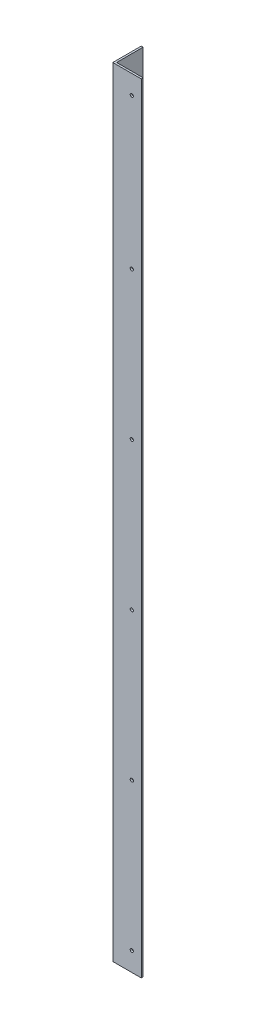
SolidWorks part; units mm, degrees
material "6063-O"
ref_plane "Piano frontale" through (0, 0, 0) normal (0, 0, 1) x (1, 0, 0)
ref_plane "Piano superiore" through (0, 0, 0) normal (0, 1, 0) x (1, 0, 0)
ref_plane "Piano destro" through (0, 0, 0) normal (1, 0, 0) x (0, 0, -1)
sketch "Schizzo2" plane through (0, 0, 0) normal (0, 1, 0) x (1, 0, 0)
  line L0 (0, 0) -> (30, 0)
  line L1 (30, 0) -> (30, 2)
  line L2 (30, 2) -> (2, 2)
  line L3 (2, 2) -> (2, 30)
  line L4 (2, 30) -> (0, 30)
  line L5 (0, 30) -> (0, 0)
  dimension "D1" = 30
  dimension "D2" = 30
  dimension "D3" = 2
  dimension "D4" = 2
extrude "Estrusione-Estrusione1" add sketch "Schizzo2" along normal blind 819
sketch "Schizzo3" plane through (0, 0, 0) normal (0, 0, 1) x (1, 0, 0)
  line L0 (20, 843.1808) -> (20, -52.7752) construction
  line L1 (0, 819) -> (0, 0) construction
  line L2 (0, 0) -> (30, 0) construction
  circle A0 centre (20, 20) radius 1.7
  circle A1 centre (20, 330.4) radius 1.7
  circle A2 centre (20, 485.6) radius 1.7
  circle A3 centre (20, 175.2) radius 1.7
  circle A4 centre (20, 640.8) radius 1.7
  circle A5 centre (20, 799) radius 1.7
  dimension "D4" = 330.4
  dimension "D8" = 3.4
  dimension "D1" = 20
  dimension "D2" = 20
  dimension "D3" = 175.2
  dimension "D5" = 485.6
  dimension "D6" = 640.8
  dimension "D7" = 799
extrude "Taglio-Estrusione1" cut sketch "Schizzo3" against normal through all
